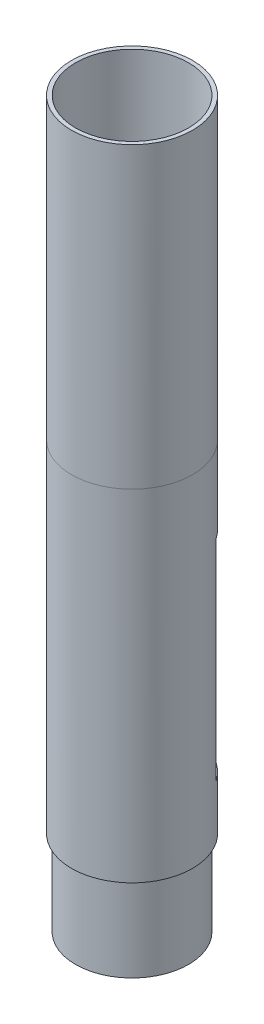
SolidWorks part; units mm, degrees
other "ChuteCoupler"
other "ChuteTube"
other "AVtube"
ref_plane "Front Plane" through (0, 0, 0) normal (0, 0, 1) x (1, 0, 0)
ref_plane "Top Plane" through (0, 0, 0) normal (0, 1, 0) x (1, 0, 0)
ref_plane "Right Plane" through (0, 0, 0) normal (1, 0, 0) x (0, 0, -1)
sketch "Sketch1" plane through (0, 0, 0) normal (0, 1, 0) x (1, 0, 0)
  circle A0 centre (0, 0) radius 28.4
  circle A2 centre (0, 0) radius 26.525
  circle A3 centre (0, 0) radius 25
  dimension "D1" = 56.8
  dimension "D2" = 53.05
  dimension "D3" = 50
extrude "Boss-Extrude1" add sketch "Sketch1" along normal blind 300 contours A0 A2 | A2 | A0 region at (-27.5967, 0, 0)
extrude "Boss-Extrude2" add sketch "Sketch1<3>" along normal blind 130 contours A2 A3 | A3 region at (-25.7748, 0, 0) region at (0, 0, 0)
sketch "Sketch1<3>" plane through (0, 0, 0) normal (0, 1, 0) x (1, 0, 0) same geometry as "Sketch1"
extrude "Boss-Extrude3" add sketch "Sketch1<4>" against normal blind 40 contours A2 A3 region at (-25.7748, 0, 0)
sketch "Sketch1<4>" plane through (0, 0, 0) normal (0, 1, 0) x (1, 0, 0) same geometry as "Sketch1"
sketch "Sketch2" plane through (0, 0, 0) normal (0, 0, 1) x (1, 0, 0)
  line L0 (0, 74.3) -> (0, 0) construction
  line L1 (23.385, 25) -> (-23.385, 25)
  line L3 (23.385, 123.6) -> (-23.385, 123.6)
  line L5 (23.385, 25) -> (-23.385, 123.6) construction
  line L6 (23.385, 123.6) -> (-23.385, 25) construction
  line L7 (-26.525, 0) -> (26.525, 0) construction
  line L8 (0, 74.3) -> (23.385, 74.3) construction
  line L9 (-23.385, 109.475) -> (-25.885, 109.475)
  line L11 (-23.385, 106.975) -> (-25.885, 106.975)
  line L12 (-25.885, 109.475) -> (-25.885, 106.975)
  line L13 (-24.635, 106.975) -> (-24.635, 109.475) construction
  line L14 (-23.385, 108.225) -> (-25.885, 108.225) construction
  line L15 (-23.385, 123.6) -> (-23.385, 109.475)
  line L16 (-23.385, 106.975) -> (-23.385, 41.625)
  line L17 (23.385, 123.6) -> (23.385, 109.475)
  line L18 (23.385, 109.475) -> (25.885, 109.475)
  line L19 (25.885, 109.475) -> (25.885, 106.975)
  line L20 (23.385, 106.975) -> (25.885, 106.975)
  line L21 (23.385, 106.975) -> (23.385, 41.625)
  line L22 (23.385, 41.625) -> (25.885, 41.625)
  line L23 (25.885, 39.125) -> (25.885, 41.625)
  line L24 (23.385, 39.125) -> (25.885, 39.125)
  line L25 (23.385, 25) -> (23.385, 39.125)
  line L26 (-23.385, 25) -> (-23.385, 39.125)
  line L27 (-23.385, 39.125) -> (-25.885, 39.125)
  line L28 (-25.885, 39.125) -> (-25.885, 41.625)
  line L29 (-23.385, 41.625) -> (-25.885, 41.625)
  line L30 (-23.385, 109.475) -> (-23.385, 106.975)
  line L31 (-23.385, 41.625) -> (-23.385, 39.125)
  line L32 (23.385, 41.625) -> (23.385, 39.125)
  line L33 (23.385, 109.475) -> (23.385, 106.975)
  point P0 (0, 74.3)
  point P28 (-23.385, 74.3)
  point P94 (-24.635, 108.225)
  dimension "D1" = 46.77
  dimension "D2" = 98.6
  dimension "D3" = 25
  dimension "D4" = 2.5
  dimension "D5" = 2.5
  dimension "D6" = 15.375
extrude "Cut-Extrude1" cut sketch "Sketch2" against normal blind 40 and the other way blind 10 contours L33 L17 L3 L15 L30 L16 L31 L26 L1 L25 L32 L21 region at (0, 74.3, 0)
sketch "Sketch3" plane through (0, 130, 0) normal (0, 1, 0) x (1, 0, 0)
  line L0 (0, -22.5) -> (0, 0) construction
  circle A0 centre (0, -22.5) radius 3.25
  dimension "D1" = 6.5
  dimension "D2" = 22.5
extrude "Cut-Extrude2" cut sketch "Sketch3" against normal through all both and the other way through all
sketch "Sketch5" plane through (0, 130, 0) normal (0, 1, 0) x (1, 0, 0)
  line L0 (0, 0) -> (0, 18) construction
  circle A0 centre (0, 18) radius 1.625
  circle A1 centre (0, 0) radius 1.625
  dimension "D2" = 3.25
  dimension "D1" = 18
extrude "Cut-Extrude4" cut sketch "Sketch5" against normal through all both and the other way through all
sketch "Sketch6" plane through (0, 0, 0) normal (0, 0, 1) x (1, 0, 0)
  line L1 (19.375, 29.3) -> (-19.375, 29.3)
  line L2 (19.375, 29.3) -> (19.375, 119.3)
  line L3 (19.375, 119.3) -> (-19.375, 119.3)
  line L4 (-19.375, 29.3) -> (-19.375, 119.3)
  line L5 (19.375, 29.3) -> (-19.375, 119.3) construction
  line L6 (19.375, 119.3) -> (-19.375, 29.3) construction
  point P0 (0, 74.3)
  dimension "D1" = 90
  dimension "D2" = 38.75
sketch "Sketch7" plane through (0, 0, 10) normal (0, 0, -1) x (-1, 0, 0)
  circle A0 centre (-19.375, 119.3) radius 1.875
  circle A1 centre (-19.375, 119.3) radius 3.475
  point P0 (-19.375, 119.3)
  point P3 (19.375, 119.3)
  point P6 (19.375, 29.3)
  point P9 (-19.375, 29.3)
  dimension "D1" = 3.75
  dimension "D2" = 1.6
sketch "Sketch9" plane through (0, 0, 10) normal (0, 0, -1) x (-1, 0, 0)
  line L0 (0, 74.3) -> (0, 0) construction
  line L1 (17.5, 44.3) -> (-17.5, 44.3)
  line L2 (17.5, 44.3) -> (17.5, 104.3)
  line L3 (17.5, 104.3) -> (-17.5, 104.3)
  line L4 (-17.5, 44.3) -> (-17.5, 104.3)
  line L5 (17.5, 44.3) -> (-17.5, 104.3) construction
  line L6 (17.5, 104.3) -> (-17.5, 44.3) construction
  line L7 (2, 44.3) -> (-2, 44.3)
  line L8 (2, 44.3) -> (2, 25)
  line L9 (2, 25) -> (-2, 25)
  line L10 (-2, 44.3) -> (-2, 25)
  line L11 (2, 44.3) -> (-2, 25) construction
  line L12 (2, 25) -> (-2, 44.3) construction
  line L13 (-23.385, 25) -> (23.385, 25) construction
  point P0 (0, 74.3)
  point P6 (0, 34.65)
  dimension "D1" = 35
  dimension "D2" = 60
  dimension "D3" = 4
extrude "Cut-Extrude5" cut sketch "Sketch9" against normal blind 6 contours L4 L1 L2 L3 | L1 L10 L8 region at (0, 74.3, 10) region at (0, 34.65, 10)
ref_plane "Plane1" through (0.8075, 0.8075, 0) normal (0.7071, 0.7071, 0) x (0, 0, -1)
sketch "Sketch10" plane through (0.8075, 0.8075, 0) normal (0.7071, 0.7071, 0) x (0, 0, -1)
  line L0 (0, 45.4492) -> (0, 0) construction
  line L1 (-16, 43.6992) -> (-10, 43.6992) construction
  circle A0 centre (0, 45.4492) radius 1.75
  dimension "D1" = 3.5
extrude "Cut-Extrude6" cut sketch "Sketch10" along normal up to next
ref_plane "Plane2" through (0, 160, 0) normal (0, -1, 0) x (-1, 0, 0)
split "Split1" trim tools "Plane2" bodies to split 111 resulting bodies 113 114
sketch "Sketch11" plane through (0, 160, 0) normal (0, -1, 0) x (-1, 0, 0)
  circle A0 centre (0, 0) radius 26.525 construction
  circle A1 centre (0, 0) radius 26.525
  circle A2 centre (0, 0) radius 26.925
  dimension "D1" = 0.4
extrude "Cut-Extrude7" cut sketch "Sketch11" against normal blind 20 and the other way blind 20
sketch "Sketch12" plane through (0, 160, 0) normal (0, -1, 0) x (-1, 0, 0)
  circle A1 centre (0, 0) radius 26.525 construction
  circle A2 centre (0, 0) radius 26.975
  circle A3 centre (0, 0) radius 26.975
  circle A4 centre (0, 0) radius 26.525
  dimension "D1" = 0.05
extrude "Boss-Extrude4" add sketch "Sketch12" along normal mid plane 39 separate body
